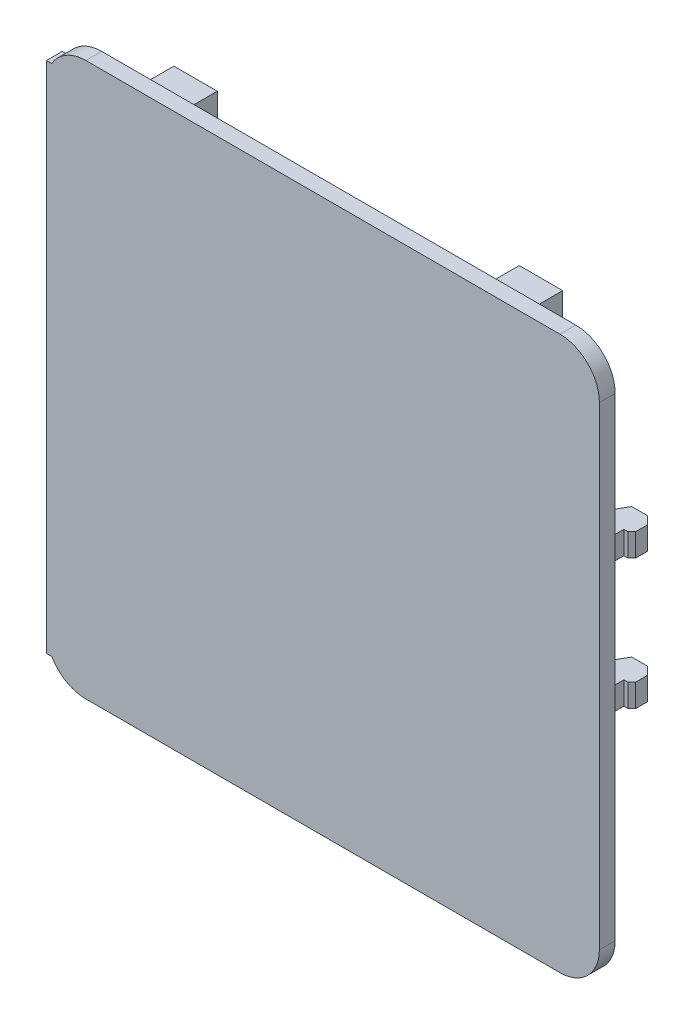
SolidWorks part; units mm, degrees
ref_plane "前视基准面" through (0, 0, 0) normal (0, 0, 1) x (1, 0, 0)
ref_plane "上视基准面" through (0, 0, 0) normal (0, 1, 0) x (1, 0, 0)
ref_plane "右视基准面" through (0, 0, 0) normal (1, 0, 0) x (0, 0, -1)
other "Configuration Table"
sketch "草图1" plane through (0, 0, 0) normal (0, 0, 1) x (1, 0, 0)
  line L0 (-30, -35) -> (30, -35) construction
  line L1 (35, -30) -> (35, 30) construction
  line L2 (30, 35) -> (-30, 35) construction
  line L3 (-30, -35) -> (30, -35)
  line L4 (35, -30) -> (35, 30)
  line L5 (30, 35) -> (-30, 35)
  line L9 (-35.8467, -30) -> (-34.8301, -30) construction
  line L10 (-35, -30) -> (-35, 30)
  line L11 (-35, -30) -> (-35, -32.5)
  line L12 (-34.3301, -32.5) -> (-35.8467, -32.5) construction
  line L13 (-35, -32.5) -> (-34.3301, -32.5)
  line L14 (-35, 30) -> (-35, 32.5)
  line L15 (-34.3301, 32.5) -> (-35.8467, 32.5) construction
  line L16 (-35, 32.5) -> (-34.3301, 32.5)
  arc A0 (30, -35) -> (35, -30) centre (30, -30) ccw construction
  arc A1 (35, 30) -> (30, 35) centre (30, 30) ccw construction
  arc A2 (30, -35) -> (35, -30) centre (30, -30) ccw
  arc A3 (35, 30) -> (30, 35) centre (30, 30) ccw
  arc A4 (-30, 35) -> (-34.3301, 32.5) centre (-30, 30) ccw
  arc A5 (-34.3301, -32.5) -> (-30, -35) centre (-30, -30) ccw
  arc A6 (-34.3301, -32.5) -> (-30, -35) centre (-30, -30) ccw construction
extrude "凸台-拉伸1" add sketch "草图1" along normal blind 2
sketch "草图2" plane through (0, 0, 0) normal (0, 0, -1) x (-1, 0, 0)
  line L0 (25.8672, -32.95) -> (25.8672, -29.95)
  line L1 (20.3672, -29.95) -> (20.3672, -32.95)
  line L2 (20.3672, -32.95) -> (25.8672, -32.95)
  line L3 (30, -35) -> (-30, -35) construction
  line L4 (20.3672, 32.95) -> (20.3672, 29.95)
  line L5 (25.8672, 29.95) -> (25.8672, 32.95)
  line L6 (25.8672, 32.95) -> (20.3672, 32.95)
  line L7 (-30, 35) -> (30, 35) construction
  line L8 (-23.357, -29.95) -> (-23.357, -32.95)
  line L9 (-23.357, -32.95) -> (-17.857, -32.95)
  line L10 (-17.857, -32.95) -> (-17.857, -29.95)
  line L11 (-23.357, 32.95) -> (-17.857, 32.95)
  line L12 (-17.857, 32.95) -> (-17.857, 29.95)
  line L13 (-23.357, 29.95) -> (-23.357, 32.95)
  arc A0 (25.8672, -29.95) -> (20.3672, -29.95) centre (23.1172, -29.95) ccw
  arc A1 (20.3672, 29.95) -> (25.8672, 29.95) centre (23.1172, 29.95) ccw
  arc A2 (-17.857, -29.95) -> (-23.357, -29.95) centre (-20.607, -29.95) ccw
  arc A3 (-17.857, 29.95) -> (-23.357, 29.95) centre (-20.607, 29.95) cw
  dimension "D1" = 2.05
  dimension "D2" = 3
  dimension "D3" = 5.5
  dimension "D4" = 2.05
  dimension "D5" = 5.5
  dimension "D6" = 3
  dimension "D7" = 2.05
  dimension "D8" = 5.5
  dimension "D9" = 3
  dimension "D10" = 5.5
  dimension "D11" = 2.05
  dimension "D12" = 3
extrude "凸台-拉伸2" add sketch "草图2" along normal blind 5
sketch "草图3" plane through (0, 0, 0) normal (0, 0, -1) x (-1, 0, 0)
  line L0 (30, -35) -> (-30, -35) construction
  line L1 (32.9, -29.95) -> (30.9, -29.95)
  line L2 (32.9, -29.95) -> (32.9, -28.05)
  line L3 (32.9, -28.05) -> (30.9, -28.05)
  line L4 (30.9, -29.95) -> (30.9, -28.05)
  line L5 (35, 32.5) -> (35, -32.5) construction
  line L6 (-30, 35) -> (30, 35) construction
  line L7 (32.9, 22.95) -> (30.9, 22.95)
  line L8 (32.9, 22.95) -> (32.9, 20.05)
  line L9 (32.9, 20.05) -> (30.9, 20.05)
  line L10 (30.9, 22.95) -> (30.9, 20.05)
  line L11 (-35, -30) -> (-35, 30) construction
  line L12 (-32.9, -4.05) -> (-30.9, -4.05)
  line L13 (-32.9, -4.05) -> (-32.9, -6.95)
  line L14 (-32.9, -6.95) -> (-30.9, -6.95)
  line L15 (-30.9, -4.05) -> (-30.9, -6.95)
  line L17 (-32.9, 12.45) -> (-30.9, 12.45)
  line L18 (-32.9, 12.45) -> (-32.9, 9.55)
  line L19 (-32.9, 9.55) -> (-30.9, 9.55)
  line L20 (-30.9, 12.45) -> (-30.9, 9.55)
  dimension "D1" = 2
  dimension "D2" = 1.9
  dimension "D3" = 5.05
  dimension "D4" = 2.1
  dimension "D5" = 2
  dimension "D6" = 2.9
  dimension "D7" = 12.05
  dimension "D8" = 2.1
  dimension "D9" = 2
  dimension "D10" = 2.9
  dimension "D11" = 28.05
  dimension "D12" = 2.1
  dimension "D13" = 2
  dimension "D14" = 2.9
  dimension "D15" = 2.1
  dimension "D16" = 22.55
extrude "凸台-拉伸3" add sketch "草图3" along normal blind 3.2
sketch "草图4" plane through (0, 0, -3.2) normal (0, 0, -1) x (-1, 0, 0)
  line L0 (32.9, -28.05) -> (30.9, -28.05) construction
  line L1 (30.9, -29.95) -> (34.05, -29.95)
  line L2 (30.9, -29.95) -> (30.9, -28.05)
  line L3 (30.9, -28.05) -> (34.05, -28.05)
  line L4 (34.05, -29.95) -> (34.05, -28.05)
  line L5 (30.9, 20.05) -> (34.05, 20.05)
  line L6 (30.9, 20.05) -> (30.9, 22.95)
  line L7 (30.9, 22.95) -> (34.05, 22.95)
  line L8 (34.05, 20.05) -> (34.05, 22.95)
  line L9 (32.9, 22.95) -> (30.9, 22.95) construction
  line L10 (-32.9, -6.95) -> (-30.9, -6.95) construction
  line L11 (-30.9, -4.05) -> (-33.9, -4.05)
  line L12 (-30.9, -4.05) -> (-30.9, -6.95)
  line L13 (-30.9, -6.95) -> (-33.9, -6.95)
  line L14 (-33.9, -4.05) -> (-33.9, -6.95)
  line L15 (-32.9, 9.55) -> (-30.9, 9.55) construction
  line L16 (-30.9, 12.45) -> (-33.9, 12.45)
  line L17 (-30.9, 12.45) -> (-30.9, 9.55)
  line L18 (-30.9, 9.55) -> (-33.9, 9.55)
  line L19 (-33.9, 12.45) -> (-33.9, 9.55)
  dimension "D1" = 3.15
  dimension "D2" = 3.15
  dimension "D3" = 3
  dimension "D4" = 3
extrude "凸台-拉伸4" add sketch "草图4" along normal blind 3
sketch "草图6" plane through (0, 0, -6.2) normal (0, 0, -1) x (-1, 0, 0)
  line L1 (30.9, 22.95) -> (34.05, 22.95)
  line L2 (30.9, 22.95) -> (30.9, 20.05)
  line L3 (30.9, 20.05) -> (34.05, 20.05)
  line L4 (34.05, 22.95) -> (34.05, 20.05)
  line L5 (30.9, -28.05) -> (34.05, -28.05)
  line L6 (30.9, -28.05) -> (30.9, -29.95)
  line L7 (30.9, -29.95) -> (34.05, -29.95)
  line L8 (34.05, -28.05) -> (34.05, -29.95)
extrude "凸台-拉伸5" add sketch "草图6" along normal blind 0.7
sketch "草图7" plane through (0, -29.95, 0) normal (0, -1, 0) x (1, 0, 0)
  line L0 (-30.9, -6.9) -> (-26.9163, 0)
  line L1 (-30, 0) -> (30, 0) construction
  line L2 (-26.9163, 0) -> (-30.9, 0)
  line L3 (-30.9, 0) -> (-30.9, -6.9)
  dimension "D1" = 60
extrude "凸台-拉伸6" add sketch "草图7" against normal up to surface (1.9 mm away) up to face at (-32.6167, -28.05, -3.3667)
sketch "草图8" plane through (0, 22.95, 0) normal (0, 1, 0) x (1, 0, 0)
  line L0 (-30.9, 6.9) -> (-26.9163, 0)
  line L1 (-26.9163, 0) -> (-30.9, 0)
  line L2 (-30.9, 0) -> (-30.9, 6.9)
extrude "凸台-拉伸7" add sketch "草图8" against normal up to surface (2.9 mm away) up to face at (-32.6167, 20.05, -3.3667)
sketch "草图9" plane through (0, 12.45, 0) normal (0, 1, 0) x (1, 0, 0)
  line L0 (30.9, 6.2) -> (27.3204, 0)
  line L1 (30, 0) -> (-30, 0) construction
  line L2 (27.3204, 0) -> (30.9, 0)
  line L3 (30.9, 0) -> (30.9, 6.2)
  dimension "D1" = 60
extrude "凸台-拉伸8" add sketch "草图9" against normal up to surface (2.9 mm away) up to face at (32.5667, 9.55, -3.1333)
sketch "草图10" plane through (0, -6.95, 0) normal (0, -1, 0) x (1, 0, 0)
  line L0 (30.9, -6.2) -> (27.3204, 0)
  line L1 (27.3204, 0) -> (30.9, 0)
  line L2 (30.9, 0) -> (30.9, -6.2)
extrude "凸台-拉伸9" add sketch "草图10" against normal up to surface (2.9 mm away) up to face at (32.5667, -4.05, -3.1333)
fillet "圆角1" radius 2 6 edges at (-29.9081, 20.05, 0) (-29.9081, 22.95, 0) (30.1102, 12.45, 0) (30.1102, -6.95, 0) (-29.9081, -29.95, 0) (-29.9081, -28.05, 0)
sketch "草图11" plane through (0, 12.45, 0) normal (0, 1, 0) x (1, 0, 0)
  line L0 (33.4, 3.2) -> (33.9, 3.7)
  line L1 (32.9, 3.2) -> (33.9, 3.2) construction
  line L2 (33.9, 6.2) -> (33.9, 3.2) construction
  line L3 (33.9, 3.7) -> (33.9, 3.2)
  line L4 (33.9, 3.2) -> (33.4, 3.2)
extrude "切除-拉伸1" cut sketch "草图11" against normal up to surface (19.4 mm away) up to face at (32.1625, -6.95, -3.8)
sketch "草图12" plane through (0, 0, 0) normal (0, 0, -1) x (-1, 0, 0)
  line L0 (-35, -30) -> (-35, 30) construction
  line L1 (-27.3, -1.7664) -> (-32, -1.7664)
  line L2 (-27.3, -1.7664) -> (-27.3, 7.2336)
  line L3 (-27.3, 7.2336) -> (-32, 7.2336)
  line L4 (-32, -1.7664) -> (-32, 7.2336)
  dimension "D1" = 3
  dimension "D2" = 4.7
  dimension "D3" = 9
extrude "凸台-拉伸10" add sketch "草图12" along normal blind 0.8
chamfer "倒角1" distance 1 angle 45 2 edges at (33.9, -5.5, -6.2) (33.9, 11, -6.2)
